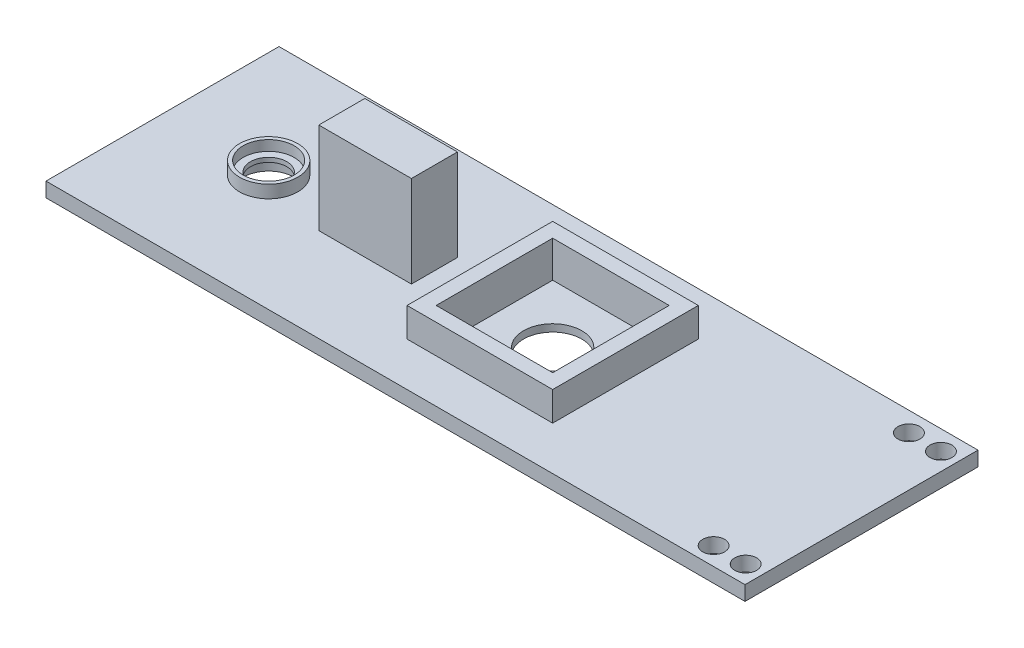
SolidWorks part; units mm, degrees
ref_plane "Front Plane" through (0, 0, 0) normal (0, 0, 1) x (1, 0, 0)
ref_plane "Top Plane" through (0, 0, 0) normal (0, 1, 0) x (1, 0, 0)
ref_plane "Right Plane" through (0, 0, 0) normal (1, 0, 0) x (0, 0, -1)
sketch "Sketch1" plane through (0, 0, 0) normal (0, 1, 0) x (1, 0, 0)
  line L1 (-304.8, -50.8) -> (0, -50.8)
  line L2 (-304.8, -50.8) -> (-304.8, 50.8)
  line L3 (-304.8, 50.8) -> (0, 50.8)
  line L4 (0, -50.8) -> (0, 50.8)
  point P0 (0, 0)
  dimension "D1" = 304.8
  dimension "D2" = 101.6
extrude "Boss-Extrude1" add sketch "Sketch1" along normal blind 6.35
sketch "Sketch2" plane through (0, 6.35, 0) normal (0, 1, 0) x (1, 0, 0)
  circle A0 centre (-258.5106, 0) radius 12.7
  point P2 (0, 0)
extrude "Boss-Extrude3" add sketch "Sketch2" along normal blind 5.5562
sketch "Sketch9" plane through (0, 11.9062, 0) normal (0, 1, 0) x (1, 0, 0)
  circle A0 centre (-258.5106, 0) radius 11.1125
extrude "Cut-Extrude4" cut sketch "Sketch9" against normal blind 4.445
sketch "Sketch10" plane through (0, 0, 0) normal (0, -1, 0) x (-1, 0, 0)
  circle A0 centre (258.5106, 0) radius 11.1125
extrude "Cut-Extrude5" cut sketch "Sketch10" against normal blind 5.5562
sketch "Sketch11" plane through (0, 7.4613, 0) normal (0, 1, 0) x (1, 0, 0)
  circle A0 centre (-258.5106, 0) radius 7.9375
extrude "Cut-Extrude6" cut sketch "Sketch11" against normal through all
sketch "Sketch12" plane through (0, 6.35, 0) normal (0, 1, 0) x (1, 0, 0)
  circle A0 centre (-134.6662, 0) radius 12.7
  point P3 (0, 0)
  point P4 (0, 0)
  point P5 (0, 0)
  point P6 (-140.3688, 0)
  point P7 (-153.4346, 0)
  point P8 (-134.6662, 0)
  dimension "D1" = 25.4
extrude "Cut-Extrude7" cut sketch "Sketch12" against normal through all
sketch "Sketch22" plane through (0, 6.35, 0) normal (0, 1, 0) x (1, 0, 0)
  line L1 (-102.9162, -31.75) -> (-166.4162, -31.75)
  line L2 (-102.9162, -31.75) -> (-102.9162, 31.75)
  line L3 (-102.9162, 31.75) -> (-166.4162, 31.75)
  line L4 (-166.4162, -31.75) -> (-166.4162, 31.75)
  line L5 (-102.9162, -31.75) -> (-166.4162, 31.75) construction
  line L6 (-102.9162, 31.75) -> (-166.4162, -31.75) construction
  circle A0 centre (-134.6662, 0) radius 12.7 construction
  point P0 (-134.6662, 0)
  point P6 (0, 0)
  point P7 (0, 0)
extrude "Boss-Extrude7" add sketch "Sketch22" along normal blind 12.7
sketch "Sketch25" plane through (0, 19.05, 0) normal (0, 1, 0) x (1, 0, 0)
  line L1 (-109.2662, -25.4) -> (-160.0662, -25.4)
  line L2 (-109.2662, -25.4) -> (-109.2662, 25.4)
  line L3 (-109.2662, 25.4) -> (-160.0662, 25.4)
  line L4 (-160.0662, -25.4) -> (-160.0662, 25.4)
  line L5 (-109.2662, -25.4) -> (-160.0662, 25.4) construction
  line L6 (-109.2662, 25.4) -> (-160.0662, -25.4) construction
  circle A0 centre (-134.6662, 0) radius 12.7 construction
  point P0 (-134.6662, 0)
  point P5 (-154.0505, 75.0031)
  point P6 (0, 0)
  point P7 (-151.3931, 0)
  point P8 (0, 0)
  point P9 (0, 0)
  dimension "D1" = 50.8
  dimension "D2" = 50.8
extrude "Cut-Extrude11" cut sketch "Sketch25" against normal blind 15.875
sketch "Sketch18" plane through (0, 6.35, 0) normal (0, 1, 0) x (1, 0, 0)
  line L2 (-226.612, -10.033) -> (-186.226, -10.033)
  line L3 (-226.612, -10.033) -> (-226.612, 10.033)
  line L4 (-226.612, 10.033) -> (-186.226, 10.033)
  line L5 (-186.226, -10.033) -> (-186.226, 10.033)
  point P7 (-258.5106, -50.4467)
extrude "Boss-Extrude5" add sketch "Sketch18" along normal blind 39.878 contours L3 L2 L5 L4
sketch "Sketch32" plane through (0, 6.35, 0) normal (0, 1, 0) x (1, 0, 0)
  line L0 (0, 50.8) -> (-304.8, 50.8) construction
  line L1 (-304.8, -50.8) -> (0, -50.8) construction
  line L2 (0, -50.8) -> (0, 50.8) construction
  circle A0 centre (-7.62, -42.8938) radius 4.7625
  circle A1 centre (-21.59, -42.8938) radius 4.7625
  circle A2 centre (-7.62, 42.2729) radius 4.7625
  circle A3 centre (-21.59, 42.2729) radius 4.7625
  point P12 (0, 0)
  point P15 (0, 0)
  point P16 (0, 0)
  dimension "D1" = 9.525
  dimension "D2" = 9.525
  dimension "D3" = 9.525
  dimension "D4" = 9.525
  dimension "D5" = 8.5271
  dimension "D6" = 7.62
  dimension "D7" = 8.5271
  dimension "D8" = 21.59
  dimension "D9" = 7.9062
  dimension "D10" = 7.62
  dimension "D11" = 7.9062
  dimension "D12" = 21.59
extrude "Cut-Extrude12" cut sketch "Sketch32" against normal blind 6.35
